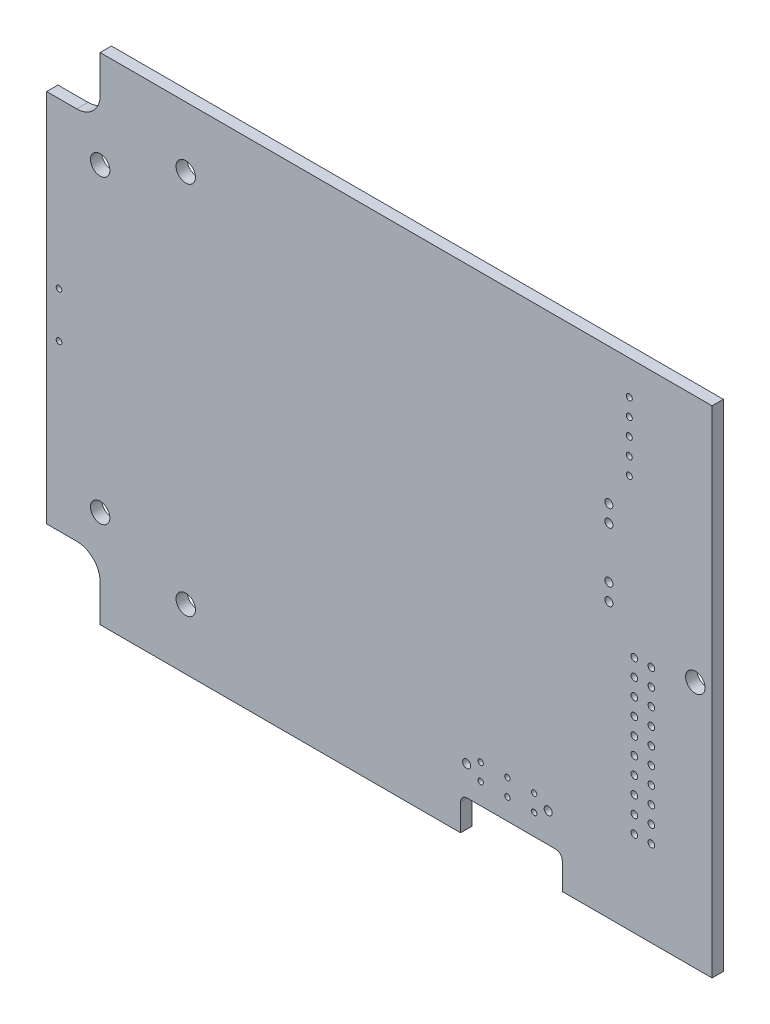
SolidWorks part; units mm, degrees
ref_plane "Płaszczyzna przednia" through (0, 0, 0) normal (0, 0, 1) x (1, 0, 0)
ref_plane "Płaszczyzna górna" through (0, 0, 0) normal (0, 1, 0) x (1, 0, 0)
ref_plane "Płaszczyzna prawa" through (0, 0, 0) normal (1, 0, 0) x (0, 0, -1)
ref_plane "Plane1" through (0, 0, 1.6894) normal (0, 0, 1) x (1, 0, 0)
sketch "Sketch1" plane through (0, 0, 1.6894) normal (0, 0, 1) x (1, 0, 0)
  line L0 (87.3, 25.4) -> (87.3, 29.4)
  line L8 (88.3, 30.4) -> (101.5, 30.4)
  line L16 (102.5, 29.4) -> (102.5, 25.4)
  line L17 (102.5, 25.4) -> (124.9, 25.4)
  line L18 (124.9, 25.4) -> (124.9, 99.5)
  line L19 (124.9, 99.5) -> (33.4, 99.5)
  line L20 (33.4, 99.5) -> (33.4, 93.95)
  line L30 (29.9, 90.45) -> (25.4, 90.45)
  line L31 (25.4, 90.45) -> (25.4, 34.45)
  line L32 (25.4, 34.45) -> (29.9, 34.45)
  line L42 (33.4, 30.95) -> (33.4, 25.4)
  line L43 (33.4, 25.4) -> (87.3, 25.4)
  arc A0 (87.3, 29.4) -> (88.3, 30.4) centre (88.3, 29.4) cw
  arc A1 (101.5, 30.4) -> (102.5, 29.4) centre (101.5, 29.4) cw
  arc A2 (29.9, 34.45) -> (33.4, 30.95) centre (29.9, 30.95) cw
  arc A3 (29.9, 90.45) -> (33.4, 93.95) centre (29.9, 93.95) ccw
extrude "Boss-Extrude1" add sketch "Sketch1" against normal blind 1.6894
hole_wizard "Ø2.9 (2.9) Diameter Hole1" positions "Sketch3" profile "Sketch2" hole size "Ø2.9" standard "ANSI Metric"
sketch "Sketch3" plane through (0, 0, 0) normal (0, 0, -1) x (-1, 0, 0)
  point P0 (-122.4, 62.45)
sketch "Sketch2" plane through (122.4, 62.45, 0) normal (1, 0, 0) x (0, 1, 0)
  line L0 (0, 0) -> (0, 1.6894)
  line L1 (0, 1.6894) -> (1.45, 1.6894)
  line L2 (1.45, 1.6894) -> (1.45, 0)
  line L5 (1.45, 0) -> (0, 0)
  line L11 (0, -6.35) -> (0, 107.95) construction
  dimension "Thru Hole Dia." = 2.9
  dimension "Thru Hole Depth" = 1.6894
hole_wizard "Hole1" positions "Sketch5" profile "Sketch4" legacy
sketch "Sketch5" plane through (0, 0, 0) normal (0, 0, -1) x (-1, 0, 0)
  point P0 (-112.522, 94.423)
sketch "Sketch4" plane through (112.522, 94.423, 0) normal (1, 0, 0) x (0, 1, 0)
  line L0 (0, 0) -> (0, 1.6894)
  line L1 (0, 1.6894) -> (0.45, 1.6894)
  line L2 (0.45, 1.6894) -> (0.45, 0)
  line L3 (0.45, 0) -> (0, 0)
  line L4 (0, 110) -> (0, -10) construction
  dimension "Diameter" = 0.9
  dimension "Depth" = 1.6894
sketch3d "3DSketch1"
  point P0 (75.7889, 62.8124, 0.8447)
  point P1 (75.7889, -37.1876, 0.8447)
ref_axis "Axis1" through (75.7889, 62.8124, 0.8447) along (0, -1, 0)
pattern_linear "LPattern1" count 5 spacing 2.54 along (0, -1, 0) of "Hole1"
hole_wizard "Hole2" positions "Sketch7" profile "Sketch6" legacy
sketch "Sketch7" plane through (0, 0, 0) normal (0, 0, -1) x (-1, 0, 0)
  point P0 (-113.284, 38.227)
sketch "Sketch6" plane through (113.284, 38.227, 0) normal (1, 0, 0) x (0, 1, 0)
  line L0 (0, 0) -> (0, 1.6894)
  line L1 (0, 1.6894) -> (0.5, 1.6894)
  line L2 (0.5, 1.6894) -> (0.5, 0)
  line L3 (0.5, 0) -> (0, 0)
  line L4 (0, 110) -> (0, -10) construction
  dimension "Diameter" = 1
  dimension "Depth" = 1.6894
sketch3d "3DSketch2"
  point P0 (175.7717, 62.8061, 0.8447)
  point P1 (75.7717, 62.8061, 0.8447)
ref_axis "Axis2" through (175.7717, 62.8061, 0.8447) along (-1, 0, 0)
sketch3d "3DSketch3"
  point P0 (75.7717, 162.8061, 0.8447)
  point P1 (75.7717, 62.8061, 0.8447)
ref_axis "Axis3" through (75.7717, 162.8061, 0.8447) along (0, -1, 0)
pattern_linear "LPattern2" count 2 spacing 2.54 along (1, 0, 0) count 10 spacing 2.54 along (0, 1, 0) of "Hole2"
hole_wizard "Hole3" positions "Sketch9" profile "Sketch8" legacy
sketch "Sketch9" plane through (0, 0, 0) normal (0, 0, -1) x (-1, 0, 0)
  point P0 (-109.479, 79.121)
sketch "Sketch8" plane through (109.479, 79.121, 0) normal (1, 0, 0) x (0, 1, 0)
  line L0 (0, 0) -> (0, 1.6894)
  line L1 (0, 1.6894) -> (0.6, 1.6894)
  line L2 (0.6, 1.6894) -> (0.6, 0)
  line L3 (0.6, 0) -> (0, 0)
  line L4 (0, 110) -> (0, -10) construction
  dimension "Diameter" = 1.2
  dimension "Depth" = 1.6894
sketch3d "3DSketch4"
  point P0 (75.6851, 62.8297, 0.8447)
  point P1 (75.4883, -37.1701, 0.8447)
ref_axis "Axis4" through (75.6851, 62.8297, 0.8447) along (-0.002, -1, 0)
pattern_linear "LPattern3" count 2 spacing 2.54 along (-0.002, -1, 0) of "Hole3"
hole_wizard "Hole4" positions "Sketch11" profile "Sketch10" legacy
sketch "Sketch11" plane through (0, 0, 0) normal (0, 0, -1) x (-1, 0, 0)
  point P0 (-109.479, 68.961)
sketch "Sketch10" plane through (109.479, 68.961, 0) normal (1, 0, 0) x (0, 1, 0)
  line L0 (0, 0) -> (0, 1.6894)
  line L1 (0, 1.6894) -> (0.6, 1.6894)
  line L2 (0.6, 1.6894) -> (0.6, 0)
  line L3 (0.6, 0) -> (0, 0)
  line L4 (0, 110) -> (0, -10) construction
  dimension "Diameter" = 1.2
  dimension "Depth" = 1.6894
sketch3d "3DSketch5"
  point P0 (75.6744, 62.8266, 0.8447)
  point P1 (75.4776, -37.1732, 0.8447)
ref_axis "Axis5" through (75.6744, 62.8266, 0.8447) along (-0.002, -1, 0)
pattern_linear "LPattern4" count 2 spacing 2.54 along (-0.002, -1, 0) of "Hole4"
hole_wizard "Ø2.9 (2.9) Diameter Hole2" positions "Sketch13" profile "Sketch12" hole size "Ø2.9" standard "ANSI Metric"
sketch "Sketch13" plane through (0, 0, 0) normal (0, 0, -1) x (-1, 0, 0)
  point P0 (-46.2, 90.45)
sketch "Sketch12" plane through (46.2, 90.45, 0) normal (1, 0, 0) x (0, 1, 0)
  line L0 (0, 0) -> (0, 1.6894)
  line L1 (0, 1.6894) -> (1.45, 1.6894)
  line L2 (1.45, 1.6894) -> (1.45, 0)
  line L5 (1.45, 0) -> (0, 0)
  line L11 (0, -6.35) -> (0, 107.95) construction
  dimension "Thru Hole Dia." = 2.9
  dimension "Thru Hole Depth" = 1.6894
hole_wizard "Ø2.9 (2.9) Diameter Hole3" positions "Sketch15" profile "Sketch14" hole size "Ø2.9" standard "ANSI Metric"
sketch "Sketch15" plane through (0, 0, 0) normal (0, 0, -1) x (-1, 0, 0)
  point P0 (-33.4, 84.95)
sketch "Sketch14" plane through (33.4, 84.95, 0) normal (1, 0, 0) x (0, 1, 0)
  line L0 (0, 0) -> (0, 1.6894)
  line L1 (0, 1.6894) -> (1.45, 1.6894)
  line L2 (1.45, 1.6894) -> (1.45, 0)
  line L5 (1.45, 0) -> (0, 0)
  line L11 (0, -6.35) -> (0, 107.95) construction
  dimension "Thru Hole Dia." = 2.9
  dimension "Thru Hole Depth" = 1.6894
hole_wizard "Ø0.85 (0.85) Diameter Hole1" positions "Sketch17" profile "Sketch16" hole size "Ø0.85" standard "ANSI Metric"
sketch "Sketch17" plane through (0, 0, 0) normal (0, 0, -1) x (-1, 0, 0)
  point P0 (-27.2501, 65.85)
sketch "Sketch16" plane through (27.2501, 65.85, 0) normal (1, 0, 0) x (0, 1, 0)
  line L0 (0, 0) -> (0, 1.6894)
  line L1 (0, 1.6894) -> (0.425, 1.6894)
  line L2 (0.425, 1.6894) -> (0.425, 0)
  line L5 (0.425, 0) -> (0, 0)
  line L11 (0, -6.35) -> (0, 107.95) construction
  dimension "Thru Hole Dia." = 0.85
  dimension "Thru Hole Depth" = 1.6894
sketch3d "3DSketch6"
  point P0 (75.7395, 62.7796, 0.8447)
  point P1 (75.7395, -37.2204, 0.8447)
ref_axis "Axis6" through (75.7395, 62.7796, 0.8447) along (0, -1, 0)
pattern_linear "LPattern5" count 2 spacing 6.8 along (0, -1, 0) of "Ø0.85 (0.85) Diameter Hole1"
hole_wizard "Hole5" positions "Sketch19" profile "Sketch18" legacy
sketch "Sketch19" plane through (0, 0, 0) normal (0, 0, -1) x (-1, 0, 0)
  point P0 (-90.3, 36.05)
sketch "Sketch18" plane through (90.3, 36.05, 0) normal (1, 0, 0) x (0, 1, 0)
  line L0 (0, 0) -> (0, 1.6894)
  line L1 (0, 1.6894) -> (0.4, 1.6894)
  line L2 (0.4, 1.6894) -> (0.4, 0)
  line L3 (0.4, 0) -> (0, 0)
  line L4 (0, 110) -> (0, -10) construction
  dimension "Diameter" = 0.8
  dimension "Depth" = 1.6894
sketch3d "3DSketch7"
  point P0 (175.7423, 62.7818, 0.8447)
  point P1 (75.7423, 62.7818, 0.8447)
ref_axis "Axis7" through (175.7423, 62.7818, 0.8447) along (-1, 0, 0)
sketch3d "3DSketch8"
  point P0 (75.7423, -37.2182, 0.8447)
  point P1 (75.7423, 62.7818, 0.8447)
ref_axis "Axis8" through (75.7423, -37.2182, 0.8447) along (0, 1, 0)
pattern_linear "LPattern6" count 3 spacing 4 along (1, 0, 0) count 2 spacing 2.5 along (0, -1, 0) of "Hole5"
hole_wizard "Ø2.9 (2.9) Diameter Hole4" positions "Sketch21" profile "Sketch20" hole size "Ø2.9" standard "ANSI Metric"
sketch "Sketch21" plane through (0, 0, 0) normal (0, 0, -1) x (-1, 0, 0)
  point P0 (-46.2, 34.45)
sketch "Sketch20" plane through (46.2, 34.45, 0) normal (1, 0, 0) x (0, 1, 0)
  line L0 (0, 0) -> (0, 1.6894)
  line L1 (0, 1.6894) -> (1.45, 1.6894)
  line L2 (1.45, 1.6894) -> (1.45, 0)
  line L5 (1.45, 0) -> (0, 0)
  line L11 (0, -6.35) -> (0, 107.95) construction
  dimension "Thru Hole Dia." = 2.9
  dimension "Thru Hole Depth" = 1.6894
hole_wizard "Hole6" positions "Sketch23" profile "Sketch22" legacy
sketch "Sketch23" plane through (0, 0, 0) normal (0, 0, -1) x (-1, 0, 0)
  point P0 (-88.2, 34.8)
sketch "Sketch22" plane through (88.2, 34.8, 0) normal (1, 0, 0) x (0, 1, 0)
  line L0 (0, 0) -> (0, 1.6894)
  line L1 (0, 1.6894) -> (0.6, 1.6894)
  line L2 (0.6, 1.6894) -> (0.6, 0)
  line L3 (0.6, 0) -> (0, 0)
  line L4 (0, 110) -> (0, -10) construction
  dimension "Diameter" = 1.2
  dimension "Depth" = 1.6894
sketch3d "3DSketch9"
  point P0 (75.7609, 62.8226, 0.8447)
  point P1 (175.7609, 62.8226, 0.8447)
ref_axis "Axis9" through (75.7609, 62.8226, 0.8447) along (1, 0, 0)
pattern_linear "LPattern7" count 2 spacing 12.2 along (1, 0, 0) of "Hole6"
hole_wizard "Ø2.9 (2.9) Diameter Hole5" positions "Sketch25" profile "Sketch24" hole size "Ø2.9" standard "ANSI Metric"
sketch "Sketch25" plane through (0, 0, 0) normal (0, 0, -1) x (-1, 0, 0)
  point P0 (-33.4, 39.95)
sketch "Sketch24" plane through (33.4, 39.95, 0) normal (1, 0, 0) x (0, 1, 0)
  line L0 (0, 0) -> (0, 1.6894)
  line L1 (0, 1.6894) -> (1.45, 1.6894)
  line L2 (1.45, 1.6894) -> (1.45, 0)
  line L5 (1.45, 0) -> (0, 0)
  line L11 (0, -6.35) -> (0, 107.95) construction
  dimension "Thru Hole Dia." = 2.9
  dimension "Thru Hole Depth" = 1.6894
